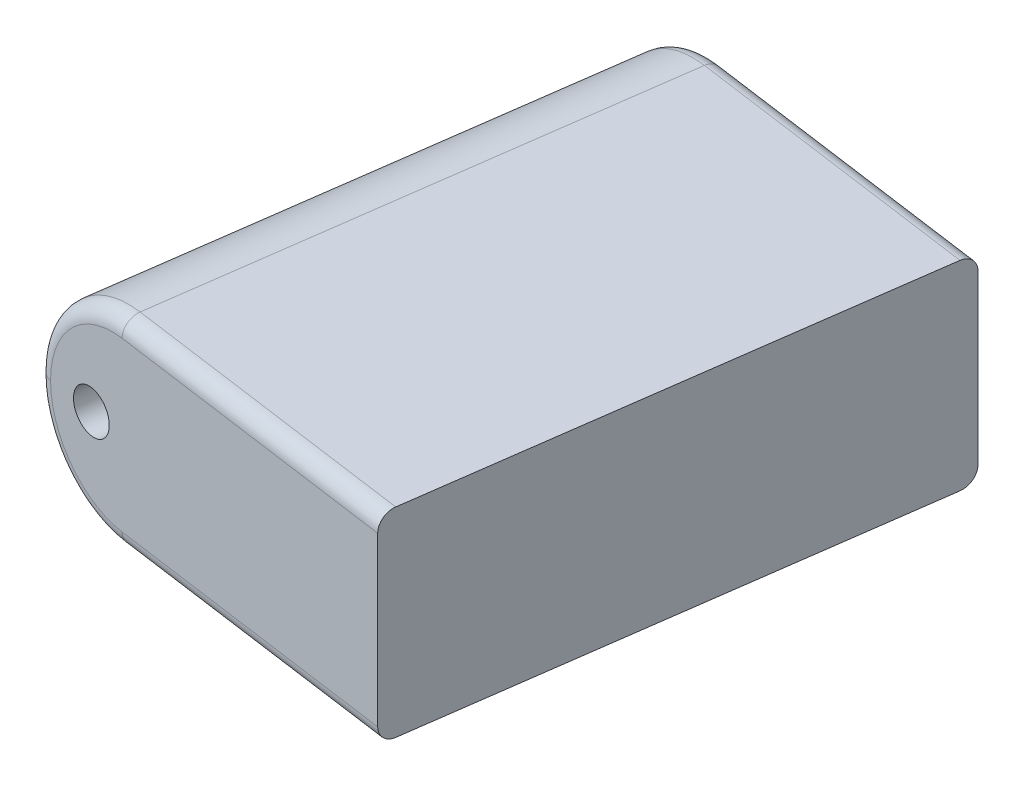
SolidWorks part; units mm, degrees
ref_plane "Front Plane" through (0, 0, 0) normal (0, 0, 1) x (1, 0, 0)
ref_plane "Top Plane" through (0, 0, 0) normal (0, 1, 0) x (1, 0, 0)
ref_plane "Right Plane" through (0, 0, 0) normal (1, 0, 0) x (0, 0, -1)
sketch "Sketch1" plane through (0, 0, 0) normal (0, 1, 0) x (1, 0, 0)
  line L12 (-29.6265, -8.5598) -> (-45.2825, -6.4414) construction
  line L13 (-26.8764, 11.317) -> (-29.6265, -8.5598) construction
  line L14 (-42.6007, 13.378) -> (-26.8764, 11.317) construction
  line L15 (-42.6007, 13.378) -> (-45.2825, -6.4414) construction
  line L20 (-27.4227, -19.1199) -> (-46.293, -16.509)
  line L21 (-23.9416, 6.0405) -> (-27.4227, -19.1199)
  line L22 (-42.8119, 8.6513) -> (-23.9416, 6.0405)
  line L23 (-42.8119, 8.6513) -> (-46.293, -16.509)
extrude "Boss-Extrude1" add sketch "Sketch1" along normal blind 9.525
sketch "Sketch3" plane through (0.3167, 0, -2.6841) normal (0.1371, 0, -0.9906) x (-0.9906, 0, -0.1371)
  line L0 (40.4955, 4.7625) -> (43.5394, 4.7625) construction
  line L1 (43.5394, 9.525) -> (43.5394, 0) construction
  line L2 (43.5394, 0) -> (43.5394, 9.525) construction
  line L3 (43.5394, 4.7625) -> (43.5394, 9.525) construction
  circle A3 centre (40.4955, 4.7625) radius 2
  point P7 (43.5394, 4.7625)
  dimension "D1" = 4
extrude "Cut-Extrude1" cut sketch "Sketch3" against normal blind 2.7
sketch "Sketch4" plane through (0.0003, 0, -0.0022) normal (0.1371, 0, -0.9906) x (-0.9906, 0, -0.1371)
  circle A0 centre (40.5497, 4.7625) radius 1
  dimension "D1" = 2
extrude "Cut-Extrude2" cut sketch "Sketch4" against normal through all
fillet "Fillet2" radius 4.7625 2 edges at (-44.5524, 0, 3.9289) (-44.5524, 9.525, 3.9289)
fillet "Fillet3" radius 0.762 8 edges at (-31.018, 0, -7.0195) (-31.018, 9.525, -7.0195) (-34.4991, 0, 18.1408) (-44.9112, 1.3949, 16.7002) (-44.9112, 8.1301, 16.7002) (-34.4991, 9.525, 18.1408) (-41.4301, 1.3949, -8.4601) (-41.4301, 8.1301, -8.4601)
